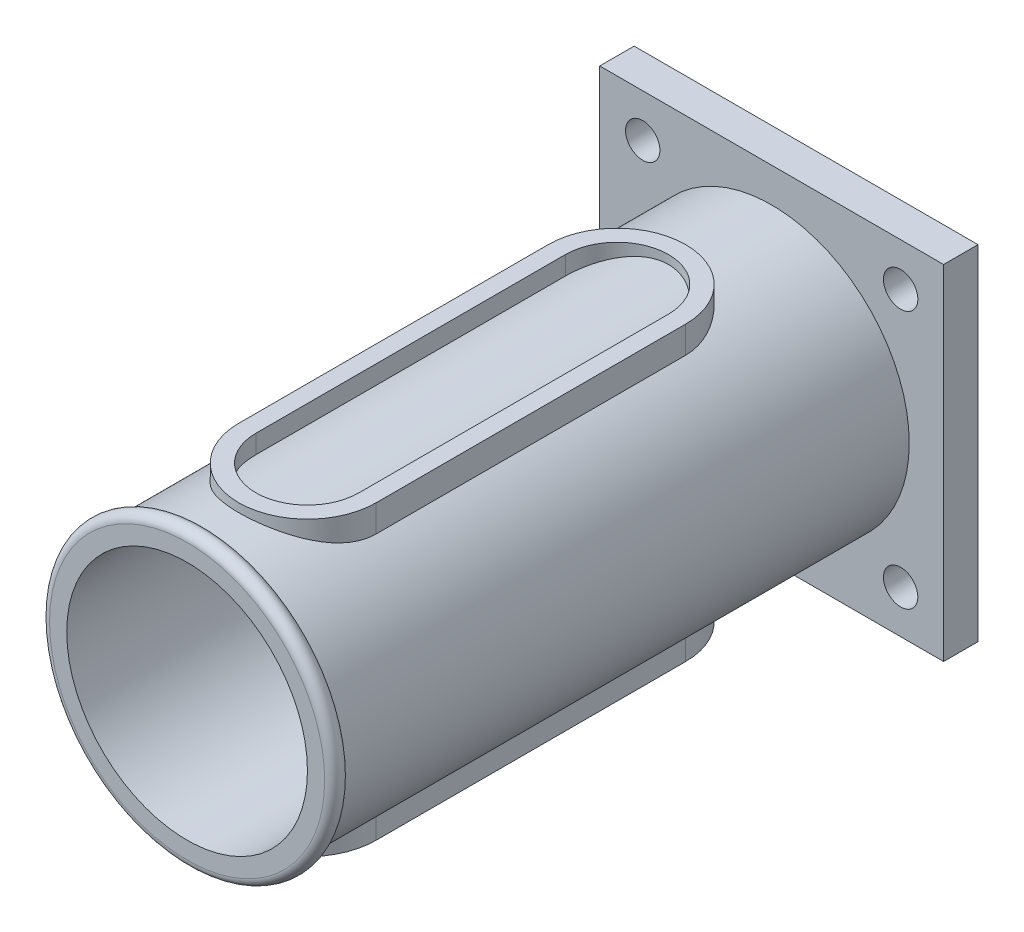
SolidWorks part; units mm, degrees
ref_plane "Front Plane" through (0, 0, 0) normal (0, 0, 1) x (1, 0, 0)
ref_plane "Top Plane" through (0, 0, 0) normal (0, 1, 0) x (1, 0, 0)
ref_plane "Right Plane" through (0, 0, 0) normal (1, 0, 0) x (0, 0, -1)
sketch "Sketch2" plane through (0, 0, 0) normal (0, 0, 1) x (1, 0, 0)
  line L1 (-31.75, -31.75) -> (31.75, -31.75)
  line L2 (-31.75, -31.75) -> (-31.75, 31.75)
  line L3 (-31.75, 31.75) -> (31.75, 31.75)
  line L4 (31.75, -31.75) -> (31.75, 31.75)
  line L5 (-31.75, -31.75) -> (31.75, 31.75) construction
  line L6 (-31.75, 31.75) -> (31.75, -31.75) construction
  circle A0 centre (0, 0) radius 22.225
  point P0 (0, 0)
extrude "Boss-Extrude1" add sketch "Sketch2" along normal blind 6.35
sketch "Sketch3" plane through (0, 0, 6.35) normal (0, 0, 1) x (1, 0, 0)
  circle A0 centre (0, 0) radius 25.4
  circle A1 centre (0, 0) radius 22.225 construction
  circle A2 centre (0, 0) radius 22.225
extrude "Boss-Extrude2" add sketch "Sketch3" along normal blind 101.6
sketch "Sketch4" plane through (0, 0, 107.95) normal (0, 0, 1) x (1, 0, 0)
  line L4 (-31.75, -31.75) -> (31.75, -31.75)
  line L5 (31.75, -31.75) -> (31.75, 31.75)
  line L6 (31.75, 31.75) -> (-31.75, 31.75)
  line L7 (-31.75, 31.75) -> (-31.75, -31.75)
  line L8 (-31.75, -31.75) -> (31.75, -31.75)
  line L9 (31.75, -31.75) -> (31.75, 31.75)
  line L10 (31.75, 31.75) -> (-31.75, 31.75)
  line L11 (-31.75, 31.75) -> (-31.75, -31.75)
  circle A1 centre (0, 0) radius 22.225
  circle A2 centre (0, 0) radius 22.225
  dimension "D1" = 0
  dimension "D2" = 0
extrude "Boss-Extrude3" add sketch "Sketch4" along normal blind 6.35
hole_wizard "#3 (0.25) Diameter Hole1" positions "Sketch5" profile "Sketch6" hole size "#3" standard "ANSI Inch" end condition up to next
sketch "Sketch5" plane through (0, 0, 0) normal (0, 0, -1) x (-1, 0, 0)
  line L0 (-31.75, 31.75) -> (31.75, 31.75) construction
  line L1 (-31.75, -31.75) -> (-31.75, 31.75) construction
  line L2 (34.925, 0) -> (-34.925, 0) construction
  line L3 (0, 34.925) -> (0, -34.925) construction
  point P0 (-23.8125, 23.8125)
  point P9 (-23.8125, -23.8125)
  point P12 (23.8125, -23.8125)
  point P13 (23.8125, 23.8125)
  dimension "D1" = 7.9375
  dimension "D2" = 7.9375
sketch "Sketch6" plane through (23.8125, 23.8125, 0) normal (1, 0, 0) x (0, 1, 0)
  line L0 (0, 0) -> (0, 6.35)
  line L1 (0, 6.35) -> (3.175, 6.35)
  line L2 (3.175, 6.35) -> (3.175, 0)
  line L5 (3.175, 0) -> (0, 0)
  line L11 (0, -6.35) -> (0, 107.95) construction
  dimension "Thru Hole Dia." = 6.35
  dimension "Thru Hole Depth" = 6.35
sketch "Sketch8" plane through (0, 0, 107.95) normal (0, 0, -1) x (-1, 0, 0)
  line L4 (31.75, -31.75) -> (31.75, 31.75)
  line L5 (31.75, 31.75) -> (-31.75, 31.75)
  line L6 (-31.75, 31.75) -> (-31.75, -31.75)
  line L7 (-31.75, -31.75) -> (31.75, -31.75)
  line L8 (31.75, -31.75) -> (31.75, 31.75)
  line L9 (31.75, 31.75) -> (-31.75, 31.75)
  line L10 (-31.75, 31.75) -> (-31.75, -31.75)
  line L11 (-31.75, -31.75) -> (31.75, -31.75)
  dimension "D1" = 0
extrude "Cut-Extrude1" cut sketch "Sketch8" against normal blind 3.175
sketch "Sketch9" plane through (0, 0, 107.95) normal (0, 0, 1) x (1, 0, 0)
  circle A1 centre (0, 0) radius 25.4
  circle A2 centre (0, 0) radius 25.4
  circle M2 centre (0, 0) radius 22.225
  circle M3 centre (0, 0) radius 25.4
  dimension "D1" = 0
extrude "Boss-Extrude4" add sketch "Sketch9" along normal up to next contours M3 M2 region at (-24.6816, 0, 107.95)
sketch "Sketch10" plane through (0, 0, 114.3) normal (0, 0, 1) x (1, 0, 0)
  circle A0 centre (0, 0) radius 26.9875
  dimension "D1" = 53.975
extrude "Cut-Extrude2" cut sketch "Sketch10" against normal blind 3.175 flip side to cut
fillet "Fillet1" 2 edges at (26.9875, 0, 111.125) (26.9875, 0, 114.3) type full round first side face at (-25.4, 0, 111.125) second side face at (22.225, 0, 114.3) middle face at (26.9875, 0, 111.125)
sketch "Sketch11" plane through (0, 0, 0) normal (0, 1, 0) x (1, 0, 0)
  line L0 (0, 0) -> (0, -143.8897) construction
  line L1 (0, -92.075) -> (0, -34.925) construction
  line L2 (-9.525, -92.075) -> (-9.525, -34.925)
  line L3 (9.525, -92.075) -> (9.525, -34.925)
  line L4 (-25.4, -6.35) -> (25.4, -6.35) construction
  line L5 (-25.4, -114.3) -> (25.4, -114.3) construction
  line L6 (-12.7, -92.075) -> (-12.7, -34.925)
  line L7 (12.7, -92.075) -> (12.7, -34.925)
  arc A0 (-9.525, -92.075) -> (9.525, -92.075) centre (0, -92.075) ccw
  arc A1 (9.525, -34.925) -> (-9.525, -34.925) centre (0, -34.925) ccw
  arc A2 (12.7, -34.925) -> (-12.7, -34.925) centre (0, -34.925) ccw
  arc A3 (-12.7, -92.075) -> (12.7, -92.075) centre (0, -92.075) ccw
  point P5 (0, -63.5)
  point P10 (0, -25.4)
  point P13 (0, -101.6)
  dimension "D2" = 19.05
  dimension "D4" = 3.175
  dimension "D1" = 19.05
  dimension "D3" = 12.7
extrude "Boss-Extrude5" add sketch "Sketch11" along normal blind 26.9875
mirror "Mirror1" about plane through (0, 0, 0) normal (0, 1, 0) of "Boss-Extrude5"
sketch "Sketch12" plane through (0, 0, 0) normal (0, 0, -1) x (-1, 0, 0)
  circle A0 centre (0, 0) radius 22.225 construction
  circle A1 centre (0, 0) radius 22.225
extrude "Cut-Extrude3" cut sketch "Sketch12" against normal through all both and the other way through all
